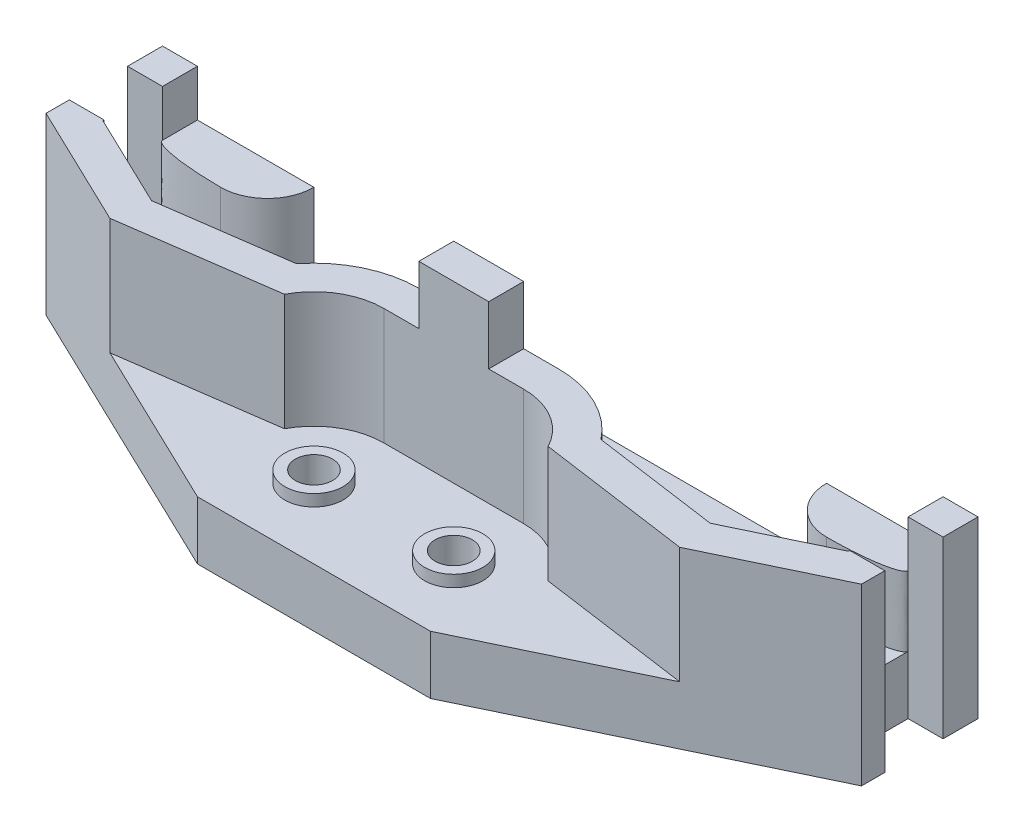
SolidWorks part; units mm, degrees
ref_plane "Front Plane" through (0, 0, 0) normal (0, 0, 1) x (1, 0, 0)
ref_plane "Top Plane" through (0, 0, 0) normal (0, 1, 0) x (1, 0, 0)
ref_plane "Right Plane" through (0, 0, 0) normal (1, 0, 0) x (0, 0, -1)
sketch "Sketch1" plane through (0, 0, 0) normal (0, 1, 0) x (1, 0, 0)
  line L0 (0, 0) -> (20, 0)
  line L1 (10, 0) -> (10, 12) construction
  line L2 (10, 12) -> (-25, 12) construction
  line L3 (0, 0) -> (-25, 12)
  line L4 (-25, 12) -> (-25, 22)
  line L5 (-25, 22) -> (45, 22)
  line L6 (45, 22) -> (45, 12)
  line L7 (45, 12) -> (20, 0)
  dimension "D1" = 35
  dimension "D2" = 20
  dimension "D3" = 12
  dimension "D4" = 70
  dimension "D5" = 10
  dimension "D6" = 10
extrude "Boss-Extrude1" add sketch "Sketch1" along normal blind 5
sketch "Sketch2" plane through (0, 5, 0) normal (0, 1, 0) x (1, 0, 0)
  line L0 (10, 0) -> (10, 22) construction
  line L1 (0, 0) -> (20, 0) construction
  line L2 (45, 22) -> (-25, 22) construction
  circle A0 centre (4, 6) radius 1.6
  circle A1 centre (16, 6) radius 1.6
  dimension "D1" = 3.2
  dimension "D2" = 6
  dimension "D3" = 6
extrude "Cut-Extrude1" cut sketch "Sketch2" against normal blind 3
sketch "Sketch3" plane through (0, 5, 0) normal (0, 1, 0) x (1, 0, 0)
  line L0 (4, 6) -> (-8.7631, 4.2063) construction
  line L1 (-25, 12) -> (0, 0) construction
  line L2 (-8.7631, 4.2063) -> (-8.7631, 22) construction
  line L3 (45, 22) -> (-25, 22) construction
  line L4 (-2.3815, 5.1031) -> (-2.8686, 8.5691) construction
  line L5 (-2.8686, 8.5691) -> (4.0027, 9.5348) construction
  line L6 (-1.3131, 8.7877) -> (-14.4587, 6.9402)
  line L7 (10, 0) -> (10, 22) construction
  line L8 (0, 0) -> (20, 0) construction
  line L10 (-14.4587, 6.9402) -> (-25, 12)
  line L11 (-25, 12) -> (-25, 22)
  line L12 (-25, 22) -> (-22, 22)
  line L13 (-21.9703, 13.8734) -> (-25, 15.3277) construction
  line L14 (-21.9703, 13.8734) -> (-9.0961, 7.6939) construction
  line L15 (-19.7294, 9.4701) -> (-13.715, 22) construction
  line L17 (-3.069, 11.5704) -> (-13.9782, 10.0372)
  line L19 (-7.8859, 7.8639) -> (-9.8726, 22) construction
  line L21 (4, 12) -> (4, 15) construction
  line L30 (-22, 22) -> (-22, 13.8877)
  line L32 (0.4296, 9.0326) -> (0.012, 12.0034) construction
  line L33 (0.012, 12.0034) -> (-19.3407, 9.2836) construction
  line L34 (-22, 13.8877) -> (-13.9782, 10.0372)
  line L35 (4, 15) -> (16, 15)
  line L36 (4, 12) -> (16, 12)
  line L37 (21.3131, 8.7877) -> (34.4587, 6.9402)
  line L38 (34.4587, 6.9402) -> (45, 12)
  line L39 (45, 12) -> (45, 22)
  line L40 (45, 22) -> (42, 22)
  line L41 (42, 22) -> (42, 13.8877)
  line L42 (42, 13.8877) -> (33.9782, 10.0372)
  line L43 (23.069, 11.5704) -> (33.9782, 10.0372)
  arc A0 (-1.3131, 8.7877) -> (4, 12) centre (4, 6) cw
  arc A4 (4, 15) -> (-3.069, 11.5704) centre (4, 6) ccw
  arc A5 (21.3131, 8.7877) -> (16, 12) centre (16, 6) ccw
  arc A6 (16, 15) -> (23.069, 11.5704) centre (16, 6) cw
  point P34 (10, 12)
  point P35 (10, 12)
  point P36 (10, 15)
  point P52 (10, 15)
  dimension "D4" = 6
  dimension "D1" = 82
  dimension "D2" = 3.5
  dimension "D3" = 90
  dimension "D5" = 90
  dimension "D6" = 90
  dimension "D7" = 3
  dimension "D8" = 3
  dimension "D9" = 3
  dimension "D10" = 3
  dimension "D11" = 3
  dimension "D12" = 90
extrude "Boss-Extrude2" add sketch "Sketch3" along normal blind 10
sketch "Sketch9" plane through (0, 15, 0) normal (0, 1, 0) x (1, 0, 0)
  line L0 (10, 12) -> (10, 15) construction
  line L1 (4, 12) -> (16, 12) construction
  line L2 (16, 15) -> (4, 15) construction
  line L3 (16, 15) -> (4, 15) construction
  line L4 (7, 12) -> (13, 12)
  line L5 (7, 12) -> (7, 15)
  line L6 (7, 15) -> (13, 15)
  line L7 (13, 12) -> (13, 15)
  dimension "D1" = 3
  dimension "D2" = 3
extrude "Boss-Extrude3" add sketch "Sketch9" along normal blind 5
sketch "Sketch12" plane through (0, 15, 0) normal (0, 1, 0) x (1, 0, 0)
  line L0 (-25, 22) -> (-25, 12) construction
  line L1 (-25, 19) -> (-22, 19)
  line L2 (-25, 19) -> (-25, 14)
  line L3 (-25, 14) -> (-22, 14)
  line L4 (-22, 19) -> (-22, 14)
  line L5 (-22, 13.8877) -> (-22, 22) construction
  line L6 (-22, 22) -> (-25, 22) construction
  line L7 (10, 22) -> (10, 0) construction
  line L8 (42, 22) -> (-22, 22) construction
  line L9 (0, 0) -> (20, 0) construction
  line L10 (45, 14) -> (42, 14)
  line L11 (42, 19) -> (42, 14)
  line L12 (45, 19) -> (42, 19)
  line L13 (45, 19) -> (45, 14)
  dimension "D1" = 3
  dimension "D2" = 5
extrude "Cut-Extrude4" cut sketch "Sketch12" against normal blind 17
sketch "Sketch14" plane through (0, 5, 0) normal (0, 1, 0) x (1, 0, 0)
  line L0 (42, 22) -> (-22, 22) construction
  line L1 (32, 22) -> (42, 22)
  line L2 (32, 22) -> (32, 18)
  line L3 (32, 18) -> (42, 18)
  line L4 (42, 22) -> (42, 18)
  line L5 (10, 22) -> (10, 0) construction
  line L6 (0, 0) -> (20, 0) construction
  line L7 (-12, 18) -> (-22, 18)
  line L8 (-22, 22) -> (-22, 18)
  line L9 (-12, 22) -> (-22, 22)
  line L10 (-12, 22) -> (-12, 18)
  dimension "D1" = 10
  dimension "D2" = 10
  dimension "D3" = 4
extrude "Boss-Extrude5" add sketch "Sketch14" along normal blind 6
fillet "Fillet3" radius 4 1 edges at (32, 8, -18) type face fillet first side face at (37, 8, -18) second side face at (32, 8, -20)
fillet "Fillet4" radius 4 1 edges at (-12, 8, -18) type face fillet first side face at (-12, 8, -20) second side face at (-17, 8, -18)
sketch "Sketch15" plane through (0, 5, 0) normal (0, 1, 0) x (1, 0, 0)
  line L0 (-12, 22) -> (-17, 29)
  line L1 (32, 22) -> (-12, 22) construction
  line L2 (-17, 29) -> (5, 29)
  line L3 (5, 29) -> (0, 22)
  line L4 (32, 22) -> (-12, 22) construction
  line L5 (-12, 22) -> (0, 22)
  line L6 (10, 22) -> (10, 29) construction
  line L7 (32, 22) -> (20, 22)
  line L8 (15, 29) -> (20, 22)
  line L9 (37, 29) -> (15, 29)
  line L10 (32, 22) -> (37, 29)
  dimension "D1" = 8
  dimension "D2" = 5
  dimension "D3" = 12
  dimension "D4" = 5
  dimension "D5" = 7
extrude "Boss-Extrude6" [suppressed] add sketch "Sketch15" against normal blind 5
sketch "Sketch18" plane through (0, 0, -12) normal (0, 0, 1) x (1, 0, 0)
  line L0 (10, 5) -> (10, 15) construction
  line L1 (0, 5) -> (20, 5) construction
  line L2 (12, 10) -> (12, 11.5)
  line L3 (12, 10) -> (8, 10)
  line L4 (10, 10) -> (10, 11.5)
  line L5 (12, 11.5) -> (8, 11.5)
  line L6 (8, 10) -> (8, 11.5)
  line L7 (4, 5) -> (16, 5) construction
  dimension "D1" = 1.5
  dimension "D2" = 2
  dimension "D3" = 5
extrude "Cut-Extrude7" [suppressed] cut sketch "Sketch18" against normal blind 3 contours L6 L3 L4 L5 | L2 L5 L4 L3
fillet "Fillet6" [suppressed] radius 1
fillet "Fillet7" [suppressed] radius 1
fillet "Fillet8" [suppressed] radius 1
fillet "Fillet9" [suppressed] radius 1
fillet "Fillet10" [suppressed] radius 1
sketch "Sketch19" plane through (0, 5, 0) normal (0, 1, 0) x (1, 0, 0)
  line L0 (0, 0) -> (20, 0) construction
  line L1 (8.5, 12) -> (11.5, 12)
  line L2 (10, 12) -> (10, 2)
  line L3 (8.5, 2) -> (11.5, 2)
  line L4 (11.5, 12) -> (11.5, 2)
  line L5 (8.5, 12) -> (8.5, 2)
  point P8 (10, 0)
  line M13 (16, 12) -> (4, 12)
  dimension "D1" = 10
  dimension "D2" = 2
  dimension "D3" = 3
  dimension "D4" = 0
extrude "Cut-Extrude8" [suppressed] cut sketch "Sketch19" against normal blind 5 contours L1 L5 L3 L2 | L4 L2 L3 M13
fillet "Fillet11" [suppressed] radius 1.5
sketch "Sketch20" plane through (0, 5, 0) normal (0, 1, 0) x (1, 0, 0)
  line L0 (10, 0) -> (10, 12) construction
  line L1 (0, 0) -> (20, 0) construction
  line L2 (7, 12) -> (13, 12) construction
  circle A0 centre (4, 6) radius 2.5
  circle A1 centre (4, 6) radius 1.6
  circle A2 centre (16, 6) radius 2.5
  circle A3 centre (16, 6) radius 1.6
  dimension "D1" = 5
extrude "Boss-Extrude7" add sketch "Sketch20" along normal blind 1
fillet "Fillet12" radius 6 1 edges at (42, 8, -18) second distance 1 first distance on face at (39, 8, -18)
fillet "Fillet13" radius 1 1 edges at (-22, 8, -18) second distance 6 first distance on face at (-22, 5.3333, -17)
sketch "Sketch21" plane through (0, 0, 0) normal (0, -1, 0) x (1, 0, 0)
  line L0 (45, -22) -> (-25, -22) construction
  line L1 (16, -22) -> (4, -22)
  line L2 (16, -22) -> (16, -12)
  line L3 (16, -12) -> (4, -12)
  line L4 (4, -22) -> (4, -12)
  point P6 (28.5003, -22)
  point P7 (14.3092, -22)
  point P8 (8.8214, -22)
  point P9 (10, -22)
  point P10 (10, -22)
  dimension "D1" = 12
  dimension "D2" = 10
extrude "Boss-Extrude9" add sketch "Sketch21" along normal blind 8
sketch "Sketch25" plane through (16, 0, 0) normal (1, 0, 0) x (0, 0, -1)
  line L0 (22, -8) -> (12, -8) construction
  line L1 (10.942, 0) -> (13.332, 0) construction
  line L2 (14.7879, -8) -> (15.61, -8) construction
  line L3 (12, 0) -> (12, -8)
  line L4 (12, -8) -> (16, -8)
  spline S0 degree 3 poles (16, -8) (14.9953, -8) (14.7066, -3.7583) (13.3144, 0) (12, 0) knots 0 0 0 0 0.541617 1 1 1 1
  dimension "D1" = 6
extrude "Cut-Extrude12" cut sketch "Sketch25" against normal up to next
sketch "Sketch22" plane through (0, 0, -22) normal (0, 0, -1) x (-1, 0, 0)
  line L0 (-4, -8) -> (-16, -8) construction
  circle A0 centre (-10, -2) radius 2.575
  point P2 (0, 0)
  point P5 (-10, -8)
  dimension "D1" = 5.15
  dimension "D2" = 6
extrude "Cut-Extrude9" cut sketch "Sketch22" against normal up to vertex (10 mm away) up to point (4, 0, -12)
sketch "Sketch23" plane through (0, 0, -22) normal (0, 0, -1) x (-1, 0, 0)
  circle A0 centre (-10, -2) radius 4.05
  dimension "D1" = 8.1
extrude "Cut-Extrude10" cut sketch "Sketch23" against normal blind 2
sketch "Sketch24" plane through (0, 0, -22) normal (0, 0, -1) x (-1, 0, 0)
  line L0 (-4, -8) -> (-4, 0) construction
  line L1 (-4, -8) -> (-16, -8) construction
  line L2 (-16, -8) -> (-16, 0) construction
  line L3 (-4, -8) -> (-4, -2)
  line L4 (-4, -8) -> (-16, -8)
  line L5 (-16, -8) -> (-16, -2)
  arc A0 (-16, -2) -> (-4, -2) centre (-10, -2) ccw
  point P1 (-16, -1.3996)
  point P9 (-4, -2)
  line M10 (-16, 0) -> (-16, -8)
  line M11 (-16, -8) -> (-4, -8)
  line M12 (-4, -8) -> (-4, 0)
extrude "Cut-Extrude11" cut sketch "Sketch24" against normal up to next contours A0 M10 M11 | A0 L4 M12 region at (5.3402, -6.6598, -22) region at (14.6598, -6.6598, -22)
